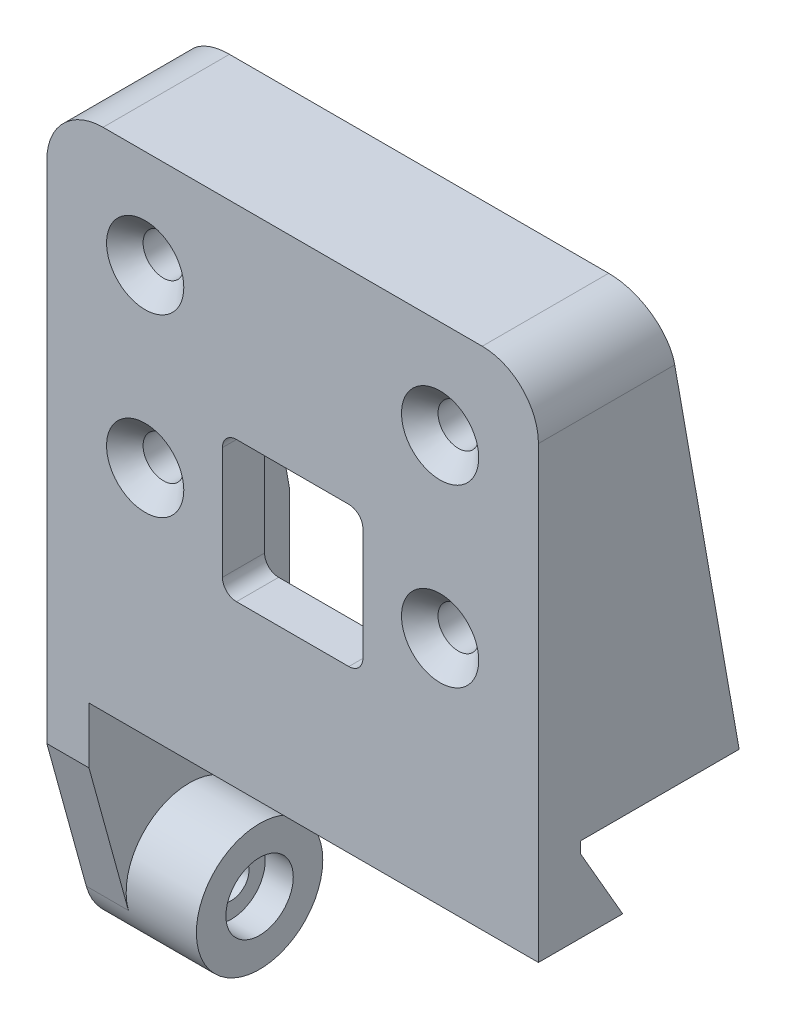
SolidWorks part; units mm, degrees
note: The reader was unsure of these and kept them because the rebuilt part matched: shared geometry of "Sketch32<4>".
material "ABS PC"
ref_plane "Front Plane" through (0, 0, 0) normal (0, 0, 1) x (1, 0, 0)
ref_plane "Top Plane" through (0, 0, 0) normal (0, 1, 0) x (1, 0, 0)
ref_plane "Right Plane" through (0, 0, 0) normal (1, 0, 0) x (0, 0, -1)
sketch "Sketch1" plane through (0, 0, 0) normal (0, 0, 1) x (1, 0, 0)
  line L1 (17.5, -15) -> (-17.5, -15)
  line L2 (17.5, -15) -> (17.5, 15)
  line L3 (17.5, 15) -> (-17.5, 15)
  line L4 (-17.5, -15) -> (-17.5, 15)
  line L5 (17.5, -15) -> (-17.5, 15) construction
  line L6 (17.5, 15) -> (-17.5, -15) construction
  point P0 (0, 0)
  dimension "D1" = 35
  dimension "D2" = 30
extrude "Boss-Extrude1" add sketch "Sketch1" against normal blind 3
sketch "Sketch2" plane through (0, 0, -3) normal (0, 0, -1) x (-1, 0, 0)
  line L9 (14.5, -12) -> (14.5, 12)
  line L10 (14.5, 12) -> (-14.5, 12)
  line L11 (-14.5, 12) -> (-14.5, -12)
  line L12 (-14.5, -12) -> (14.5, -12)
  line L13 (14.5, -12) -> (14.5, 12)
  line L14 (14.5, 12) -> (-14.5, 12)
  line L15 (-14.5, 12) -> (-14.5, -12)
  line L16 (-14.5, -12) -> (14.5, -12)
  line L22 (17.5, -15) -> (17.5, 15)
  line L23 (17.5, 15) -> (-17.5, 15)
  line L24 (-17.5, 15) -> (-17.5, -15)
  line L25 (-17.5, -15) -> (17.5, -15)
  line L26 (17.5, -15) -> (17.5, 15)
  line L27 (17.5, 15) -> (-17.5, 15)
  line L28 (-17.5, 15) -> (-17.5, -15)
  line L29 (-17.5, -15) -> (17.5, -15)
  dimension "D1" = 3
  dimension "D2" = 0
extrude "Boss-Extrude2" add sketch "Sketch2" along normal blind 3
sketch "Sketch3" plane through (0, 0, 0) normal (0, 0, 1) x (1, 0, 0)
  line L0 (0, -15) -> (0, -4.5) construction
  line L1 (-17.5, -15) -> (17.5, -15) construction
  line L2 (-14.5, 12) -> (14.5, 12) construction
  line L3 (-5, -9.5) -> (5, -9.5)
  line L4 (-5, -9.5) -> (-5, 0.5)
  line L5 (-5, 0.5) -> (5, 0.5)
  line L6 (5, -9.5) -> (5, 0.5)
  line L7 (-5, -9.5) -> (5, 0.5) construction
  line L8 (-5, 0.5) -> (5, -9.5) construction
  dimension "D1" = 10
  dimension "D2" = 16.5
extrude "Cut-Extrude1" cut sketch "Sketch3" against normal blind 3
hole_wizard "CSK for M2.5 Flat Head Machine Screw1" positions "Sketch9" profile "Sketch10" countersink size "M2.5" standard "ANSI Metric"
sketch "Sketch9" plane through (0, 0, 0) normal (0, 0, 1) x (1, 0, 0)
  line L3 (-10.5, -4.5) -> (10.5, -4.5)
  line L4 (-10.5, -4.5) -> (-10.5, 8)
  line L5 (-10.5, 8) -> (10.5, 8)
  line L6 (10.5, -4.5) -> (10.5, 8)
  line L7 (-10.5, -4.5) -> (10.5, 8) construction
  line L8 (-10.5, 8) -> (10.5, -4.5) construction
  line L10 (17.5, 15) -> (-17.5, 15) construction
  line L11 (0, -4.5) -> (0, 0) construction
  point P5 (10.5, 8)
  point P8 (-10.5, -4.5)
  point P9 (-10.5, 8)
  point P10 (10.5, -4.5)
  dimension "D1" = 12.5
  dimension "D2" = 21
  dimension "D3" = 7
sketch "Sketch10" plane through (10.5, 8, 0) normal (1, 0, 0) x (0, -1, 0)
  line L0 (0, 0) -> (0, 5.8712)
  line L1 (0, 5.8712) -> (1.45, 5)
  line L2 (1.45, 5) -> (1.45, 1.3)
  line L3 (1.45, 1.3) -> (2.75, 0)
  line L5 (2.75, 0) -> (0, 0)
  line L6 (-1.45, 1.3) -> (-2.75, 0) construction
  line L10 (0, 5.8712) -> (-1.45, 5) construction
  line L11 (0, -6.35) -> (0, 107.95) construction
  dimension "Hole Dia." = 2.9
  dimension "Hole Depth" = 5
  dimension "Near C'Sink Dia." = 5.5
  dimension "Near C'Sink Angle" = 90
  dimension "Drill Angle" = 118
sketch "Sketch11" plane through (-17.5, 0, 0) normal (-1, 0, 0) x (0, 0, 1)
  line L0 (-6, 15) -> (-9, 15)
  line L1 (-9, 15) -> (-14.2898, -15)
  line L2 (-14.2898, -15) -> (-6, -15)
  line L4 (-6, -15) -> (-6, 15)
  dimension "D1" = 3
  dimension "D2" = 10
extrude "Boss-Extrude4" add sketch "Sketch11" against normal blind 3
hole_wizard "Ø3.5 (3.5) Diameter Hole1" [suppressed] positions "Sketch12" profile "Sketch13" hole size "Ø3.5" standard "ANSI Metric"
sketch "Sketch12" plane through (-16.5, 0, 0) normal (-1, 0, 0) x (0, 0, 1)
  line L0 (-8.0249, -7.4838) -> (-8.9122, -12.5162) construction
  line L2 (-8, 20) -> (-15.0531, -20) construction
  line L3 (-12.4686, -10) -> (-8.4686, -10) construction
  line L4 (-15.0531, -20) -> (0, -20) construction
  point P0 (-8.0249, -7.4838)
  point P1 (-8.9122, -12.5162)
  dimension "D1" = 5.11
  dimension "D2" = 4
  dimension "D3" = 10
sketch "Sketch13" plane through (-16.5, -7.4838, -8.0249) normal (0, 1, 0) x (0, 0, 1)
  line L0 (0, 0) -> (0, 6.0515)
  line L1 (0, 6.0515) -> (1.75, 5)
  line L2 (1.75, 5) -> (1.75, 0)
  line L5 (1.75, 0) -> (0, 0)
  line L10 (0, 6.0515) -> (-1.75, 5) construction
  line L11 (0, -6.35) -> (0, 107.95) construction
  dimension "Hole Dia." = 3.5
  dimension "Hole Depth" = 5
  dimension "Drill Angle" = 118
mirror "Mirror1" about plane through (0, 0, 0) normal (1, 0, 0) of "Boss-Extrude4"
fillet "Fillet1" radius 1 4 edges at (-5, -9.5, -1.5) (5, -9.5, -1.5) (-5, 0.5, -1.5) (5, 0.5, -1.5)
sketch "Sketch15" plane through (0, 0, -6) normal (0, 0, -1) x (-1, 0, 0)
  line L1 (-14.5, 12) -> (14.5, 12)
  line L2 (-14.5, 12) -> (-14.5, 15)
  line L3 (-14.5, 15) -> (14.5, 15)
  line L4 (14.5, 12) -> (14.5, 15)
extrude "Boss-Extrude5" add sketch "Sketch15" along normal up to surface (3.529 mm away) up to face at (16, 0, -11.6449)
sketch "Sketch16" plane through (0, -15, 0) normal (0, -1, 0) x (1, 0, 0)
  line L0 (14.5, -9.529) -> (14.5, -3) construction
  line L1 (-14.5, -6) -> (14.5, -6)
  line L2 (-14.5, -6) -> (-14.5, -3)
  line L3 (-14.5, -3) -> (14.5, -3)
  line L4 (14.5, -6) -> (14.5, -3)
  line L5 (14.5, -6) -> (-14.5, -6) construction
  line L6 (-17.5, 0) -> (17.5, 0) construction
  dimension "D1" = 3
extrude "Cut-Extrude6" cut sketch "Sketch16" against normal blind 3 contours L3 L4 L1 L2
sketch "Sketch17" [suppressed] plane through (16.5, 0, 0) normal (1, 0, 0) x (0, 0, -1)
  line L0 (8.0249, -7.4838) -> (8.9122, -12.5162) construction
  circle A0 centre (8.4686, -10) radius 3
  dimension "D1" = 6
extrude "Cut-Extrude7" [suppressed] cut sketch "Sketch17" against normal blind 3
sketch "Sketch18" plane through (0, 1.9914, -11.2938) normal (0, 0.1736, -0.9848) x (-1, 0, 0)
  line L0 (14.5, 10.163) -> (-14.5, 10.163) construction
  line L1 (-14.5, -21.837) -> (14.5, -21.837)
  line L2 (-14.5, -21.837) -> (-14.5, -11.837)
  line L3 (-14.5, -11.837) -> (14.5, -11.837)
  line L4 (14.5, -21.837) -> (14.5, -11.837)
  line L7 (-14.5, 10.163) -> (-14.5, -17.2535) construction
  line L8 (14.5, 10.163) -> (14.5, -17.2535) construction
  dimension "D1" = 10
  dimension "D2" = 22
extrude "Boss-Extrude6" [suppressed] add sketch "Sketch18" against normal blind 3
sketch "Sketch19" plane through (0, 0, 0) normal (0, 0, 1) x (1, 0, 0)
  line L1 (-17.5, -15) -> (17.5, -15)
  line L2 (-17.5, -15) -> (-17.5, -24.0275)
  line L3 (-17.5, -24.0275) -> (17.5, -24.0275)
  line L4 (17.5, -15) -> (17.5, -24.0275)
extrude "Cut-Extrude8" [suppressed] cut sketch "Sketch19" against normal through all
chamfer "Chamfer4" [suppressed] distance 2 angle 45
sketch "Sketch20" [suppressed] plane through (-16.5, 0, 0) normal (-1, 0, 0) x (0, 0, 1)
  line L0 (-8.0249, -7.4838) -> (-8.9122, -12.5162) construction
  line L1 (-8.9122, -12.5162) -> (-8.0249, -7.4838) construction
  line L2 (-10.6357, -12.2123) -> (-9.7483, -7.1799)
  line L3 (-7.1888, -12.8201) -> (-6.3015, -7.7877)
  arc A0 (-10.6357, -12.2123) -> (-7.1888, -12.8201) centre (-8.9122, -12.5162) ccw
  arc A1 (-6.3015, -7.7877) -> (-9.7483, -7.1799) centre (-8.0249, -7.4838) ccw
  circle A2 centre (-8.0249, -7.4838) radius 1.75 construction
  point P5 (-8.4686, -10)
extrude "Cut-Extrude9" [suppressed] cut sketch "Sketch20" against normal blind 3
fillet "Fillet2" radius 4 2 edges at (17.5, 15, -4.5) (-17.5, 15, -4.5)
fillet "Fillet3" radius 2 2 edges at (-14.5, 12, -6.2645) (14.5, 12, -6.2645)
sketch "Sketch21" plane through (-17.5, 0, 0) normal (-1, 0, 0) x (0, 0, 1)
  line L1 (-14.2898, -15) -> (0, -15)
  line L2 (-14.2898, -15) -> (-14.2898, -40)
  line L3 (-14.2898, -40) -> (0, -40)
  line L4 (0, -15) -> (0, -40)
  dimension "D1" = 25
extrude "Boss-Extrude7" add sketch "Sketch21" against normal up to surface (3 mm away) up to face at (-14.5, -2.5, -7.5429)
sketch "Sketch22" plane through (-17.5, 0, 0) normal (-1, 0, 0) x (0, 0, 1)
  line L0 (-7.1449, -34.555) -> (-7.1449, -29.445) construction
  line L1 (-8.6449, -34.555) -> (-8.6449, -29.445)
  line L2 (-5.6449, -34.555) -> (-5.6449, -29.445)
  line L3 (-7.1449, -34.555) -> (-7.1449, -40) construction
  line L4 (-14.2898, -40) -> (0, -40) construction
  arc A0 (-8.6449, -34.555) -> (-5.6449, -34.555) centre (-7.1449, -34.555) ccw
  arc A1 (-5.6449, -29.445) -> (-8.6449, -29.445) centre (-7.1449, -29.445) ccw
  point P2 (-7.1449, -32)
  dimension "D1" = 5.11
  dimension "D2" = 8
  dimension "D3" = 3
extrude "Cut-Extrude10" [suppressed] cut sketch "Sketch22" against normal blind 10
sketch "Sketch23" plane through (0, 0, 0) normal (0, 0, 1) x (1, 0, 0)
  line L1 (-14.5, -15) -> (17.5, -15)
  line L2 (-14.5, -15) -> (-14.5, -21)
  line L3 (-14.5, -21) -> (17.5, -21)
  line L4 (17.5, -15) -> (17.5, -21)
  dimension "D1" = 6
extrude "Boss-Extrude8" add sketch "Sketch23" against normal blind 3
chamfer "Chamfer5" [suppressed] distance 3 angle 30
sketch "Sketch24" plane through (0, 0, 0) normal (0, 0, 1) x (1, 0, 0)
  line L0 (0, -10.5048) -> (0, -23.4952) construction
  line L1 (0, -10.5048) -> (-7.5, -23.4952)
  line L2 (-7.5, -23.4952) -> (7.5, -23.4952)
  line L3 (0, -10.5048) -> (7.5, -23.4952)
  point P6 (0, -17)
  dimension "D1" = 15
  dimension "D2" = 17
extrude "Cut-Extrude11" [suppressed] cut sketch "Sketch24" against normal blind 3
fillet "Fillet4" [suppressed] radius 2
chamfer "Chamfer6" [suppressed] distance 1 angle 45
sketch "Sketch25" plane through (0, 0, 0) normal (0, 0, 1) x (1, 0, 0)
  line L0 (0, -9.5695) -> (0, -22.3789) construction
  line L1 (-1, -8.4148) -> (-3, -7.2601)
  line L2 (-7, -8.4148) -> (-9, -7.2601)
  line L3 (-9, -7.2601) -> (-11, -8.4148)
  line L4 (-11, -8.4148) -> (-11, -10.7242)
  line L5 (-11, -10.7242) -> (-9, -11.8789)
  line L6 (-9, -11.8789) -> (-7, -10.7242)
  line L7 (-7, -10.7242) -> (-7, -8.4148)
  line L8 (-3, -7.2601) -> (-5, -8.4148)
  line L9 (-5, -8.4148) -> (-5, -10.7242)
  line L10 (-5, -10.7242) -> (-3, -11.8789)
  line L11 (-3, -11.8789) -> (-1, -10.7242)
  line L12 (-1, -10.7242) -> (-1, -8.4148)
  line L13 (1, -10.7242) -> (1, -8.4148)
  line L14 (3, -11.8789) -> (1, -10.7242)
  line L15 (5, -10.7242) -> (3, -11.8789)
  line L16 (5, -8.4148) -> (5, -10.7242)
  line L17 (3, -7.2601) -> (5, -8.4148)
  line L18 (7, -10.7242) -> (7, -8.4148)
  line L19 (9, -11.8789) -> (7, -10.7242)
  line L20 (11, -10.7242) -> (9, -11.8789)
  line L21 (11, -8.4148) -> (11, -10.7242)
  line L22 (9, -7.2601) -> (11, -8.4148)
  line L23 (7, -8.4148) -> (9, -7.2601)
  line L24 (1, -8.4148) -> (3, -7.2601)
  line L25 (-3, -9.5695) -> (-9, -9.5695) construction
  line L26 (0, -12.4563) -> (-2, -13.611)
  line L27 (-6, -12.4563) -> (-8, -13.611)
  line L28 (-8, -13.611) -> (-8, -15.9204)
  line L29 (-8, -15.9204) -> (-6, -17.0751)
  line L30 (-6, -17.0751) -> (-4, -15.9204)
  line L31 (-4, -15.9204) -> (-4, -13.611)
  line L32 (-4, -13.611) -> (-6, -12.4563)
  line L33 (-2, -13.611) -> (-2, -15.9204)
  line L34 (-2, -15.9204) -> (0, -17.0751)
  line L35 (0, -17.0751) -> (2, -15.9204)
  line L36 (2, -15.9204) -> (2, -13.611)
  line L37 (2, -13.611) -> (0, -12.4563)
  line L38 (6, -12.4563) -> (4, -13.611)
  line L39 (4, -13.611) -> (4, -15.9204)
  line L40 (4, -15.9204) -> (6, -17.0751)
  line L41 (6, -17.0751) -> (8, -15.9204)
  line L42 (8, -15.9204) -> (8, -13.611)
  line L43 (8, -13.611) -> (6, -12.4563)
  line L44 (-3, -14.7657) -> (3, -14.7657) construction
  line L45 (-3, -19.9618) -> (-9, -19.9618) construction
  line L46 (1, -21.1165) -> (3, -22.2712)
  line L47 (7, -21.1165) -> (9, -22.2712)
  line L48 (9, -22.2712) -> (11, -21.1165)
  line L49 (11, -21.1165) -> (11, -18.8071)
  line L50 (11, -18.8071) -> (9, -17.6524)
  line L51 (9, -17.6524) -> (7, -18.8071)
  line L52 (7, -18.8071) -> (7, -21.1165)
  line L53 (3, -22.2712) -> (5, -21.1165)
  line L54 (5, -21.1165) -> (5, -18.8071)
  line L55 (5, -18.8071) -> (3, -17.6524)
  line L56 (3, -17.6524) -> (1, -18.8071)
  line L57 (1, -18.8071) -> (1, -21.1165)
  line L58 (-1, -18.8071) -> (-1, -21.1165)
  line L59 (-3, -17.6524) -> (-1, -18.8071)
  line L60 (-5, -18.8071) -> (-3, -17.6524)
  line L61 (-5, -21.1165) -> (-5, -18.8071)
  line L62 (-3, -22.2712) -> (-5, -21.1165)
  line L63 (-7, -18.8071) -> (-7, -21.1165)
  line L64 (-9, -17.6524) -> (-7, -18.8071)
  line L65 (-11, -18.8071) -> (-9, -17.6524)
  line L66 (-11, -21.1165) -> (-11, -18.8071)
  line L67 (-9, -22.2712) -> (-11, -21.1165)
  line L68 (-7, -21.1165) -> (-9, -22.2712)
  line L69 (-1, -21.1165) -> (-3, -22.2712)
  circle A0 centre (-9, -9.5695) radius 2 construction
  circle A1 centre (-3, -9.5695) radius 2 construction
  circle A2 centre (3, -9.5695) radius 2 construction
  circle A3 centre (9, -9.5695) radius 2 construction
  circle A4 centre (-6, -14.7657) radius 2 construction
  circle A5 centre (0, -14.7657) radius 2 construction
  circle A6 centre (6, -14.7657) radius 2 construction
  circle A7 centre (9, -19.9618) radius 2 construction
  circle A8 centre (3, -19.9618) radius 2 construction
  circle A9 centre (-3, -19.9618) radius 2 construction
  circle A10 centre (-9, -19.9618) radius 2 construction
  point P40 (-6, -9.5695)
  point P94 (-6, -19.9618)
  dimension "D1" = 4
  dimension "D3" = 6
  dimension "D4" = 6
  dimension "D5" = 2
  dimension "D6" = 2
  dimension "D7" = 2
  dimension "D2" = 2
  dimension "D8" = 3
extrude "Cut-Extrude12" [suppressed] cut sketch "Sketch25" against normal blind 10
sketch "Sketch27" plane through (17.5, 0, 0) normal (1, 0, 0) x (0, 0, -1)
  line L0 (3, -21) -> (3, -15.8038)
  line L1 (3, -21) -> (3, -15) construction
  line L2 (3, -15.8038) -> (6, -21)
  line L4 (6, -21) -> (3, -21)
  dimension "D1" = 3
  dimension "D2" = 30
extrude "Boss-Extrude10" add sketch "Sketch27" against normal up to surface (32 mm away) up to face at (-14.5, -16.7143, -6.3516)
sketch "Sketch28" plane through (0, 0, 0) normal (0, 0, 1) x (1, 0, 0)
  line L0 (-14.5, -21) -> (-14.5, -40)
  line L1 (-14.5, -40) -> (-14.5, -21) construction
  line L2 (-14.5, -40) -> (4.5, -21)
  line L3 (-14.5, -21) -> (17.5, -21) construction
  line L4 (4.5, -21) -> (-14.5, -21)
extrude "Boss-Extrude11" [suppressed] add sketch "Sketch28" against normal up to vertex
sketch "Sketch30" plane through (-17.5, 0, 0) normal (-1, 0, 0) x (0, 0, 1)
  line L0 (-14.2898, -34) -> (0, -34) construction
  line L1 (-14.2898, -15) -> (-14.2898, -40) construction
  line L2 (0, 11) -> (0, -40) construction
  line L3 (-14.2898, -40) -> (0, -40) construction
  circle A0 centre (-7.1449, -34) radius 1.25
  dimension "D1" = 2.5
  dimension "D2" = 6
extrude "Cut-Extrude13" cut sketch "Sketch30" against normal through all
chamfer "Chamfer9" [suppressed] distance 10 angle 30
sketch "Sketch32" plane through (-14.5, 0, 0) normal (1, 0, 0) x (0, 0, -1)
  circle A0 centre (7.1449, -34) radius 1.25
  circle A1 centre (7.1449, -34) radius 1.25 construction
  circle A2 centre (7.1449, -34) radius 2.4
  circle A3 centre (7.1449, -34) radius 4.5
  circle M1 centre (7.1449, -34) radius 1.25
  dimension "D1" = 4.8
  dimension "D2" = 9
extrude "Boss-Extrude12" add sketch "Sketch32" along normal blind 5 contours A3 A2
sketch "Sketch33" plane through (-17.5, 0, 0) normal (-1, 0, 0) x (0, 0, 1)
  circle A0 centre (-7.1449, -34) radius 2.75
  dimension "D1" = 5.5
extrude "Cut-Extrude15" cut sketch "Sketch33" against normal blind 4.5
extrude "Boss-Extrude13" add sketch "Sketch32<4>" along normal blind 3 contours A2 M1
sketch "Sketch32<4>" plane through (-14.5, 0, 0) normal (1, 0, 0) x (0, 0, -1) same geometry as "Sketch32"
sketch "Sketch34" plane through (-17.5, 0, 0) normal (-1, 0, 0) x (0, 0, 1)
  circle A0 centre (-7.1449, -34) radius 2.75
extrude "Cut-Extrude17" cut sketch "Sketch34" against normal up to surface (4.5 mm away) up to face at (-13, -34, -4.7449)
sketch "Sketch35" plane through (-14.5, 0, 0) normal (1, 0, 0) x (0, 0, -1)
  line L0 (2.8063, -35.1943) -> (0, -25)
  line L1 (0, -40) -> (0, -21) construction
  line L2 (0, -25) -> (0, -40)
  line L3 (7.1449, -34) -> (7.1449, -40) construction
  line L4 (14.2898, -40) -> (0, -40) construction
  line L5 (0, -40) -> (14.2898, -40)
  line L6 (14.2898, -25) -> (14.2898, -40)
  line L7 (11.4835, -35.1943) -> (14.2898, -25)
  circle A0 centre (7.1449, -34) radius 4.5 construction
  arc A1 (2.8063, -35.1943) -> (11.4835, -35.1943) centre (7.1449, -34) ccw
  point P15 (3.151, -35.2215)
  dimension "D1" = 15
extrude "Cut-Extrude18" cut sketch "Sketch35" against normal through all
